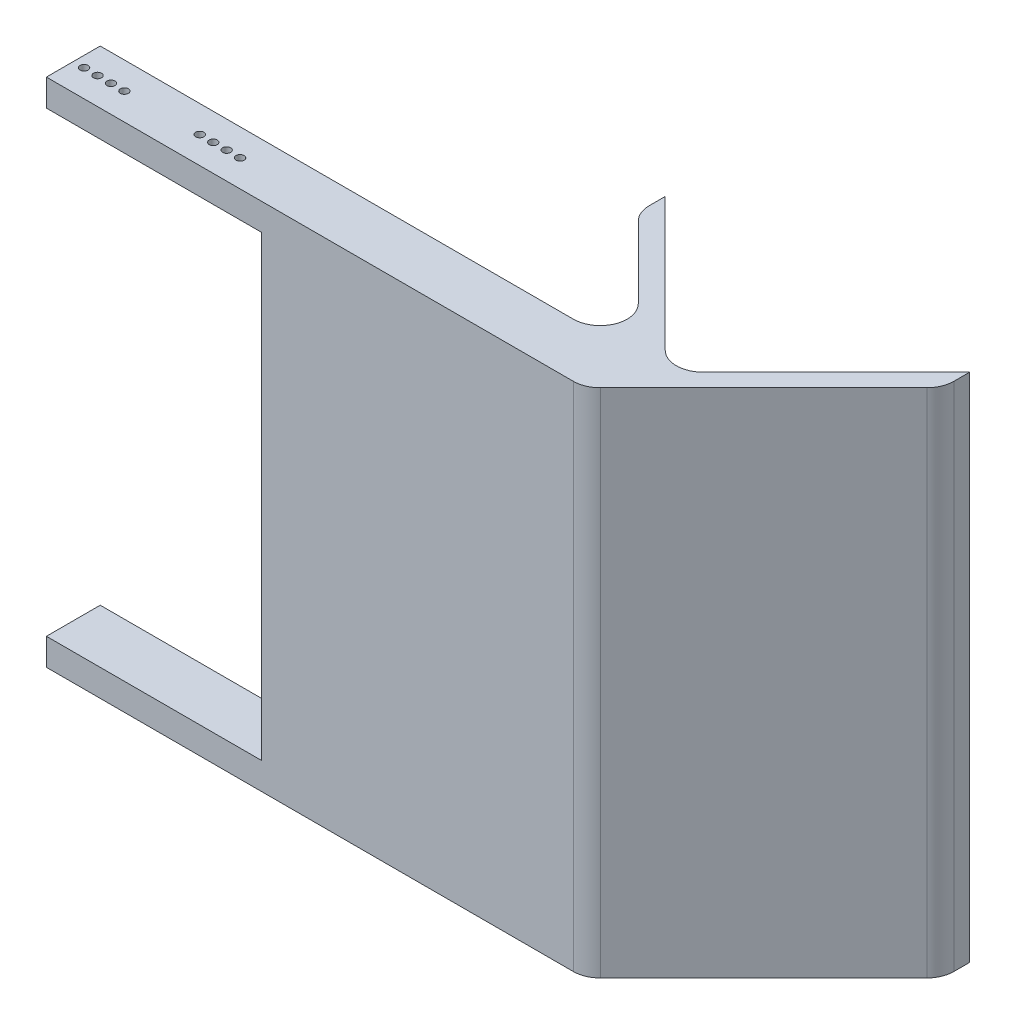
SolidWorks part; units mm, degrees
other "Marquage1"
sketch "Esquisse6" plane through (-75, 0, -38.2843) normal (-0.024, -0.0063, -0.9997) x (-0.9942, -0.1051, 0.0245)
ref_plane "Front Plane" through (0, 0, 0) normal (0, 0, 1) x (1, 0, 0)
ref_plane "Top Plane" through (0, 0, 0) normal (0, 1, 0) x (1, 0, 0)
ref_plane "Right Plane" through (0, 0, 0) normal (1, 0, 0) x (0, 0, -1)
sketch "Sketch1" plane through (0, 0, 0) normal (0, 1, 0) x (1, 0, 0)
  line L0 (-55, 0) -> (55, 0) construction
  line L1 (30, 0) -> (-75, 0)
  line L4 (-75, 0) -> (-75, 10)
  line L5 (30, 10) -> (58.2843, 38.2843)
  line L6 (58.2843, 38.2843) -> (58.2843, 33.2843)
  line L7 (58.2843, 33.2843) -> (35, 10)
  line L8 (30, 10) -> (1.7157, 38.2843)
  line L9 (1.7157, 38.2843) -> (1.7157, 33.2843)
  line L10 (1.7157, 33.2843) -> (25, 10)
  line L11 (35, 10) -> (25, 0)
  line L12 (-75, 10) -> (25, 10)
  line L13 (25, 0) -> (-75, 0)
  dimension "D10" = 10
  dimension "D1" = 30
  dimension "D2" = 30
  dimension "D3" = 75
  dimension "D4" = 10
  dimension "D5" = 33.2843
  dimension "D6" = 58.2843
  dimension "D7" = 225
  dimension "D8" = 33.2843
  dimension "D9" = 28.2843
  dimension "D11" = 90
  dimension "D12" = 45
  dimension "D13" = 5
extrude "Boss-Extrude3" add sketch "Sketch1" along normal blind 95 contours L4 L12 L10 L9 L8 L5 L6 L7 L11 L13
fillet "Fillet7" radius 5 1 edges at (30, 47.5, -10)
fillet "Fillet8" radius 5 1 edges at (25, 47.5, -10)
fillet "Fillet9" radius 5 2 edges at (58.2843, 47.5, -33.2843) (1.7157, 47.5, -33.2843)
fillet "Fillet10" radius 5 1 edges at (25, 47.5, 0)
sketch "Esquisse3" plane through (0, 0, -10) normal (0, 0, -1) x (-1, 0, 0)
  line L0 (75, 95) -> (75, 0) construction
  line L1 (75, 5) -> (45, 5)
  line L2 (75, 5) -> (75, 90)
  line L3 (75, 90) -> (45, 90)
  line L4 (45, 5) -> (45, 90)
  line L5 (75, 0) -> (-12.9289, 0) construction
  line L6 (75, 95) -> (-12.9289, 95) construction
  dimension "D1" = 5
  dimension "D2" = 5
  dimension "D3" = 30
extrude "Enlèv. mat.-Extru.1" cut sketch "Esquisse3" against normal through all contours L2 L1 L4 L3
sketch "Esquisse4" plane through (0, 90, 0) normal (0, -1, 0) x (1, 0, 0)
  line L0 (-75, -10) -> (-45, -10) construction
  line L1 (-75, 0) -> (-75, -10) construction
  line L2 (-75, 0) -> (-45, 0) construction
  circle A0 centre (-73, -5) radius 0.75
  circle A1 centre (-68, -5) radius 0.75
  circle A2 centre (-70.5, -5) radius 0.75
  circle A3 centre (-65.5, -5) radius 0.75
  circle A4 centre (-46.5, -5) radius 0.75
  circle A5 centre (-49, -5) radius 0.75
  circle A7 centre (-51.5, -5) radius 0.75
  dimension "D1" = 1.5
  dimension "D2" = 5
  dimension "D11" = 5
  dimension "D3" = 2
  dimension "D4" = 2.5
  dimension "D5" = 2.5
  dimension "D6" = 2.5
  dimension "D7" = 5
  dimension "D8" = 5
  dimension "D9" = 5
  dimension "D10" = 14
  dimension "D12" = 10
  dimension "D13" = 2.5
  dimension "D14" = 2.5
sketch "Esquisse5" plane through (0, 0, -10) normal (0, 0, -1) x (-1, 0, 0)
  line L1 (45, 5) -> (35, 5)
  line L2 (45, 5) -> (45, 65)
  line L3 (45, 65) -> (35, 65)
  line L4 (35, 5) -> (35, 65)
  dimension "D1" = 10
extrude "Enlèv. mat.-Extru.2" cut sketch "Esquisse5" against normal through all contours L2 L1 L4 L3
sketch "Esquisse13" plane through (0, 90, 0) normal (0, -1, 0) x (-1, 0, 0)
  line L0 (75, 10) -> (45, 10) construction
  circle A0 centre (44, 5) radius 0.75
  dimension "D1" = 2.5
  dimension "D2" = 5
extrude "Enlèv. mat.-Extru.3" cut sketch "Esquisse13" against normal blind 10
extrude "Enlèv. mat.-Extru.6" cut sketch "Esquisse4" against normal blind 10
sketch "Esquisse14" plane through (0, 0, -10) normal (0, 0, -1) x (-1, 0, 0)
  line L0 (45, 65) -> (35, 65) construction
  line L1 (45, 90) -> (35, 90)
  line L2 (45, 90) -> (45, 65)
  line L3 (45, 65) -> (35, 65)
  line L4 (35, 90) -> (35, 65)
  point P8 (8.5101, 69.7264)
extrude "Enlèv. mat.-Extru.7" cut sketch "Esquisse14" against normal through all
